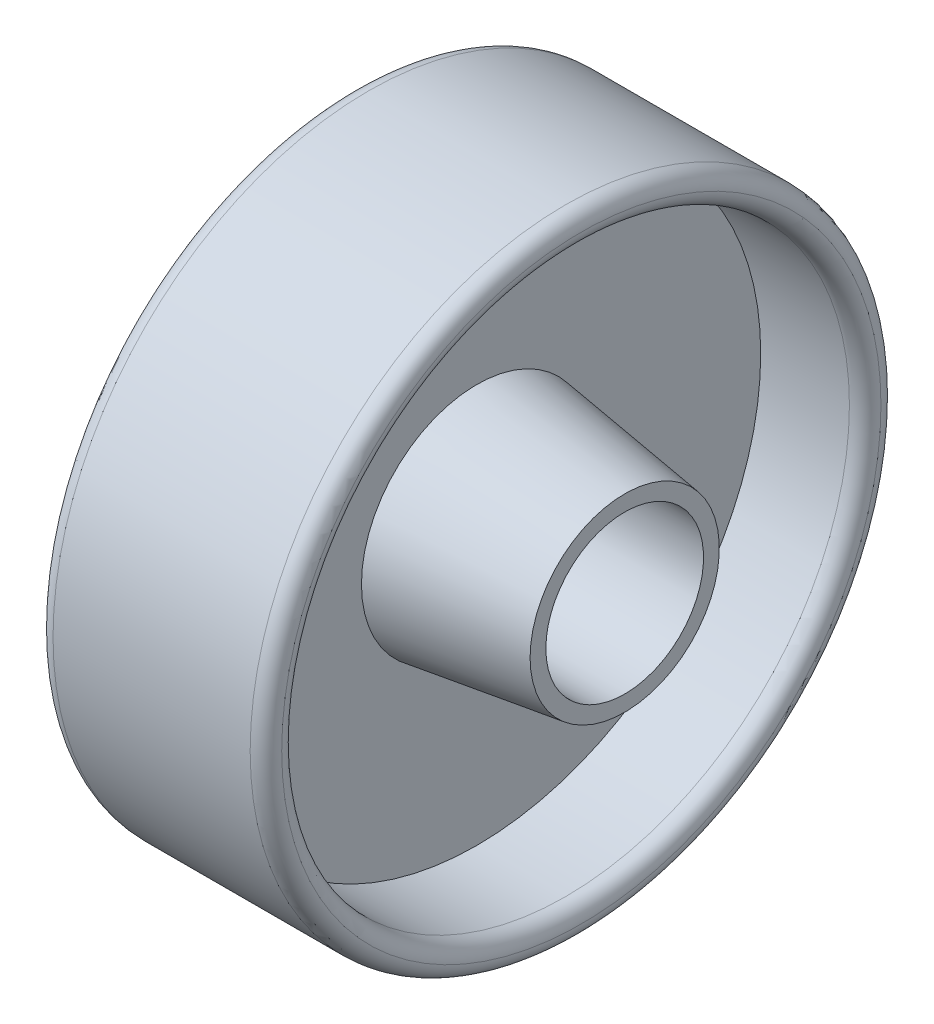
SolidWorks part; units mm, degrees
ref_plane "Front Plane" through (0, 0, 0) normal (0, 0, 1) x (1, 0, 0)
ref_plane "Top Plane" through (0, 0, 0) normal (0, 1, 0) x (1, 0, 0)
ref_plane "Right Plane" through (0, 0, 0) normal (1, 0, 0) x (0, 0, -1)
sketch "Sketch2" plane through (0, 0, 0) normal (0, 0, 1) x (1, 0, 0)
  line L0 (-20, 10) -> (20, 10)
  line L1 (20, 10) -> (20, 12)
  line L2 (20, 12) -> (1.25, 14.6351)
  line L3 (1.25, 14.6351) -> (1.25, 36)
  line L4 (1.25, 36) -> (14.5, 36)
  line L5 (14.5, 36) -> (14.5, 40)
  line L6 (14.5, 40) -> (-14.5, 40)
  line L7 (0, 10) -> (0, 36.8601) construction
  line L8 (-14.5, 36) -> (-14.5, 40)
  line L9 (-1.25, 36) -> (-14.5, 36)
  line L10 (-1.25, 14.6351) -> (-1.25, 36)
  line L11 (-20, 12) -> (-1.25, 14.6351)
  line L12 (-20, 10) -> (-20, 12)
  line L13 (0, 0) -> (83.9085, 0) construction
  line L14 (83.9085, 0) -> (-78.3476, 0) construction
  point P13 (0, 40)
  dimension "D1" = 20
  dimension "D2" = 10
  dimension "D3" = 2
  dimension "D4" = 14.5
  dimension "D5" = 4
  dimension "D6" = 2.5
  dimension "D7" = 8
  dimension "D8" = 40
revolve "Revolve1" add sketch "Sketch2" angle 360 about L13
fillet "Fillet1" radius 2 4 edges at (14.5, 0, 36) (-14.5, 0, 36) (14.5, 0, 40) (-14.5, 0, 40)
